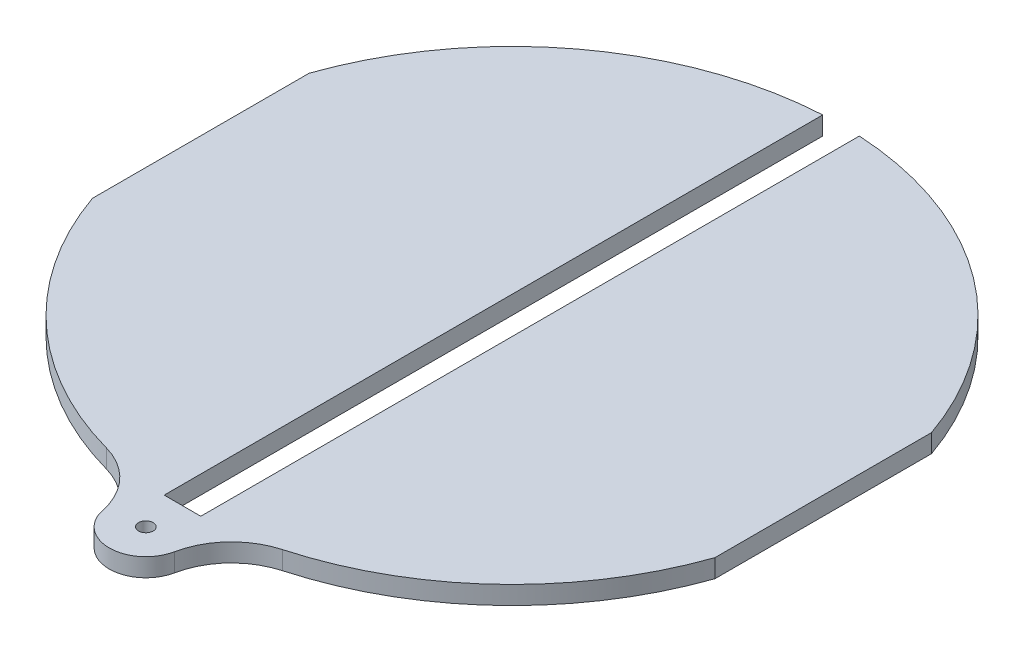
SolidWorks part; units mm, degrees
ref_plane "Front Plane" through (0, 0, 0) normal (0, 0, 1) x (1, 0, 0)
ref_plane "Top Plane" through (0, 0, 0) normal (0, 1, 0) x (1, 0, 0)
ref_plane "Right Plane" through (0, 0, 0) normal (1, 0, 0) x (0, 0, -1)
sketch "Sketch2" plane through (0, 0, 0) normal (0, 1, 0) x (1, 0, 0)
  line L0 (3.175, 60.325) -> (53.975, 60.325)
  line L1 (-53.975, -60.325) -> (-6.35, -60.325)
  line L2 (-53.975, -60.325) -> (-53.975, 60.325)
  line L3 (-53.975, 60.325) -> (-3.175, 60.325)
  line L4 (53.975, -60.325) -> (53.975, 60.325)
  line L5 (-53.975, -60.325) -> (53.975, 60.325) construction
  line L6 (-53.975, 60.325) -> (53.975, -60.325) construction
  line L7 (-3.175, -53.975) -> (3.175, -53.975)
  line L8 (-3.175, -53.975) -> (-3.175, 60.325)
  line L10 (3.175, -53.975) -> (3.175, 60.325)
  line L11 (-3.175, -53.975) -> (3.175, 60.325) construction
  line L12 (-3.175, 60.325) -> (3.175, -53.975) construction
  line L13 (6.35, -60.325) -> (53.975, -60.325)
  arc A0 (-6.35, -60.325) -> (6.35, -60.325) centre (0, -60.325) ccw
  point P0 (0, 0)
  point P6 (0, 3.175)
  dimension "D1" = 120.65
  dimension "D2" = 107.95
  dimension "D3" = 6.35
  dimension "D4" = 114.3
extrude "Boss-Extrude1" add sketch "Sketch2" along normal blind 3.175 contours L3 L8 L7 L10 L0 L4 L13 A0 L1 L2
sketch "Sketch3" plane through (0, 3.175, 0) normal (0, 1, 0) x (1, 0, 0)
  circle A0 centre (0, -60.325) radius 1.27
  dimension "D1" = 2.54
extrude "Cut-Extrude1" cut sketch "Sketch3" against normal through all
sketch "Sketch4" plane through (0, 3.175, 0) normal (0, 1, 0) x (1, 0, 0)
  line L0 (-3.175, 3.175) -> (83.1266, 3.175) construction
  line L2 (-3.175, -53.975) -> (-3.175, 60.325) construction
  line L7 (0, 0) -> (0, 96.6328) construction
  line L8 (3.175, 60.325) -> (53.975, 60.325) construction
  line L9 (-6.35, -60.325) -> (-6.35, -53.6211)
  line L10 (-53.975, 60.325) -> (53.975, 60.325)
  line L11 (-53.975, 60.325) -> (-53.975, 21.9586)
  line L12 (-53.975, -60.325) -> (-6.35, -60.325)
  line L13 (53.975, 60.325) -> (53.975, 21.9586)
  line L14 (6.35, -60.325) -> (6.35, -53.6211)
  line L15 (53.975, -15.6086) -> (53.975, -60.325)
  line L16 (-53.975, -15.6086) -> (-53.975, -60.325)
  line L17 (6.35, -60.325) -> (53.975, -60.325)
  arc A1 (-53.975, -15.6086) -> (-6.35, -53.6211) centre (0, 3.175) ccw
  arc A2 (53.975, 21.9586) -> (-53.975, 21.9586) centre (0, 3.175) ccw
  arc A3 (6.35, -53.6211) -> (53.975, -15.6086) centre (0, 3.175) ccw
  line M11 (-53.975, 60.325) -> (-53.975, -60.325)
  line M12 (-53.975, -60.325) -> (-6.35, -60.325)
  line M14 (6.35, -60.325) -> (53.975, -60.325)
  line M15 (53.975, -60.325) -> (53.975, 60.325)
  line M16 (53.975, 60.325) -> (3.175, 60.325)
  line M17 (3.175, 60.325) -> (3.175, -53.975)
  line M19 (-3.175, -53.975) -> (-3.175, 60.325)
  line M20 (-3.175, 60.325) -> (-53.975, 60.325)
extrude "Cut-Extrude2" cut sketch "Sketch4" against normal through all both and the other way through all contours A1 L9 M11 M12 | A2 M19 M20 M11 | A3 L14 M14 M15 | A2 M15 M16 M17 region at (-37.5733, 3.175, 48.3954) region at (37.5733, 3.175, 48.3954) region at (-41.542, 3.175, -50.0186) region at (41.542, 3.175, -50.0186)
fillet "Fillet1" radius 12.7 2 edges at (6.35, 1.5875, 53.6211) (-6.35, 1.5875, 53.6211)
